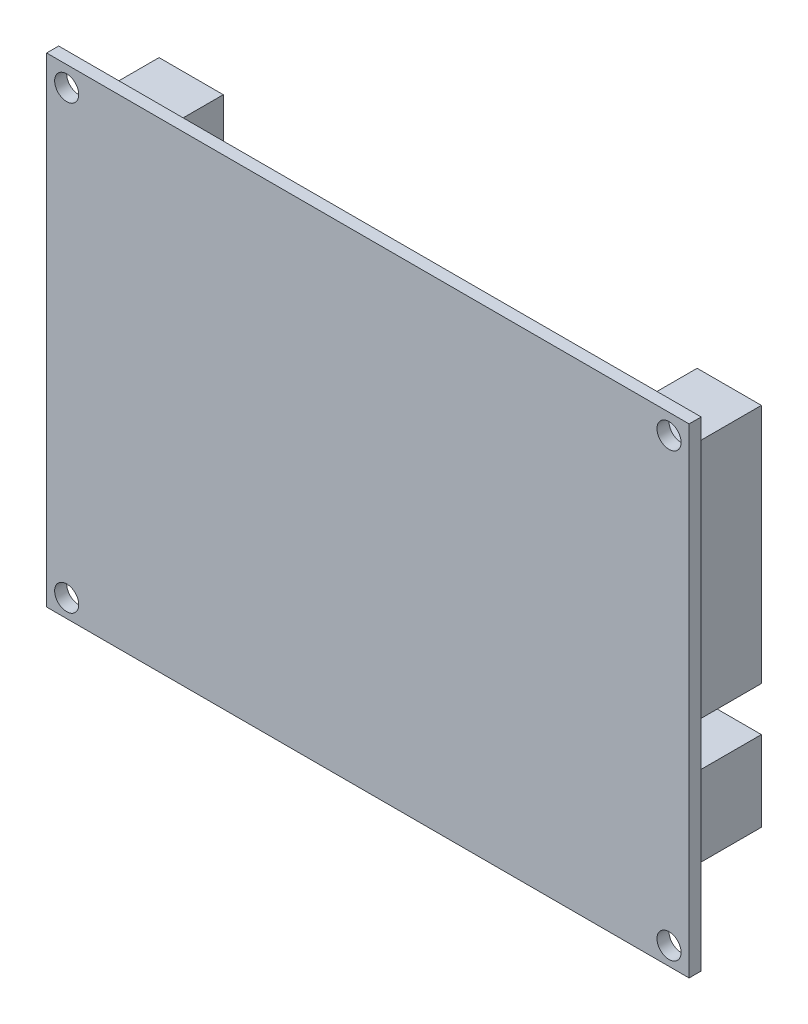
SolidWorks part; units mm, degrees
ref_plane "Front Plane" through (0, 0, 0) normal (0, 0, 1) x (1, 0, 0)
ref_plane "Top Plane" through (0, 0, 0) normal (0, 1, 0) x (1, 0, 0)
ref_plane "Right Plane" through (0, 0, 0) normal (1, 0, 0) x (0, 0, -1)
sketch "Sketch1" plane through (0, 0, 0) normal (0, 0, 1) x (1, 0, 0)
  line L0 (-35.4983, 34.528) -> (39.5017, 34.528)
  line L1 (-37.9983, 37.028) -> (42.0017, 37.028)
  line L2 (-37.9983, 37.028) -> (-37.9983, -22.972)
  line L3 (-37.9983, -22.972) -> (42.0017, -22.972)
  line L4 (42.0017, 37.028) -> (42.0017, -22.972)
  line L5 (39.5017, 34.528) -> (39.5017, -20.472)
  line L6 (-35.4983, -20.472) -> (39.5017, -20.472)
  line L7 (-35.4983, 34.528) -> (-35.4983, -20.472)
  line L8 (-37.9983, 32.028) -> (42.0017, 32.028)
  line L9 (39.5017, -3.472) -> (31.5017, -3.472)
  line L10 (39.5017, 32.028) -> (31.5017, 32.028)
  line L11 (39.5017, 32.028) -> (39.5017, 2.028)
  line L12 (39.5017, 2.028) -> (31.5017, 2.028)
  line L13 (31.5017, 32.028) -> (31.5017, 2.028)
  line L14 (-37.9983, -22.722) -> (42.0017, -22.722)
  line L15 (31.5017, -3.472) -> (39.5017, -3.472)
  line L16 (31.5017, -3.472) -> (31.5017, -13.472)
  line L17 (31.5017, -13.472) -> (39.5017, -13.472)
  line L18 (39.5017, -3.472) -> (39.5017, -13.472)
  line L19 (-35.4983, -14.472) -> (-15.4983, -14.472)
  line L20 (-35.4983, -22.722) -> (-15.4983, -22.722)
  line L21 (-35.4983, -22.722) -> (-35.4983, -14.722)
  line L22 (-35.4983, -14.722) -> (-15.4983, -14.722)
  line L23 (-15.4983, -22.722) -> (-15.4983, -14.722)
  line L24 (-37.9983, 19.028) -> (42.0017, 19.028)
  line L25 (-35.4983, -14.472) -> (-28.4983, -14.472)
  line L26 (-35.4983, -14.472) -> (-35.4983, -6.472)
  line L27 (-35.4983, -6.472) -> (-28.4983, -6.472)
  line L28 (-28.4983, -14.472) -> (-28.4983, -6.472)
  line L30 (-35.4983, 19.028) -> (14.5017, 19.028)
  line L31 (-35.4983, 19.028) -> (-35.4983, -5.972)
  line L32 (-35.4983, -5.972) -> (14.5017, -5.972)
  line L33 (14.5017, 19.028) -> (14.5017, -5.972)
  line L34 (-35.4983, 32.028) -> (-27.4983, 32.028)
  line L35 (-35.4983, 32.028) -> (-35.4983, 22.028)
  line L36 (-35.4983, 22.028) -> (-27.4983, 22.028)
  line L37 (-27.4983, 32.028) -> (-27.4983, 22.028)
  circle A0 centre (-35.4983, 34.528) radius 1.5
  circle A1 centre (39.5017, 34.528) radius 1.5
  circle A2 centre (-35.4983, -20.472) radius 1.5
  circle A3 centre (39.5017, -20.472) radius 1.5
  dimension "D4" = 5
  dimension "D1" = 60
  dimension "D2" = 80
  dimension "D5" = 8
  dimension "D6" = 30
  dimension "D8" = 10
  dimension "D10" = 8
  dimension "D11" = 20
  dimension "D13" = 7
  dimension "D14" = 8
  dimension "D16" = 25
  dimension "D17" = 50
  dimension "D18" = 10
  dimension "D19" = 8
  dimension "D3" = 2.5
  dimension "D7" = 5.5
  dimension "D9" = 0.25
  dimension "D12" = 0.25
  dimension "D15" = 18
extrude "Boss-Extrude1" add sketch "Sketch1" against normal blind 1.5 contours L8 L37 L36 L7 L24 L13 | A1 L5 L8 L4 L1 L2 L7 A0 L0 | A1 L0 A0 L7 L8 L5 | L2 L24 L7 L8 | L37 L8 L7 L36 | A2 L7 L24 L2 L14 L21 | L33 L24 L7 L32 | A3 L5 L17 L16 L9 L12 L13 L24 L33 L32 L7 L27 L28 L19 L22 L23 L6 | L13 L24 L5 L8 | L24 L13 L12 L11 | L5 L24 L4 L8 | A3 L6 L23 L14 L4 L24 L11 L5 | L16 L17 L5 L9 | A2 L6 L23 L22 L7 | A2 L21 L14 L23 L6 | L19 L28 L27 L7 region at (2.0017, 35.6777, 0) region at (2.0017, 33.2662, 0) region at (-31.4983, 27.028, 0) region at (-36.7483, 25.528, 0) region at (0.9852, 25.3763, 0) region at (40.7517, 25.528, 0) region at (35.5017, 25.528, 0) region at (-10.4983, 6.528, 0) region at (-36.7698, -1.1942, 0) region at (40.7517, 18.3174, 0) region at (35.5017, 10.528, 0) region at (12.1173, -6.3516, 0) region at (-31.9983, -10.472, 0) region at (-25.1156, -21.617, 0) region at (35.5017, -8.472, 0) region at (-25.3522, -17.5621, 0)
extrude "Boss-Extrude2" add sketch "Sketch1<8>" against normal blind 1.5 from offset 1.75 separate body contours L33 L24 L7 L32 region at (-10.4983, 6.528, 0) offset against normal yes
sketch "Sketch1<8>" plane through (0, 0, 0) normal (0, 0, 1) x (1, 0, 0) same geometry as "Sketch1"
extrude "Boss-Extrude3" add sketch "Sketch1<9>" against normal blind 10 from surface contours L37 L8 L7 L36 | L13 L24 L5 L8 | L24 L13 L12 L11 | L16 L17 L5 L9 | A2 L6 L23 L22 L7 | A2 L21 L14 L23 L6 region at (-31.4983, 27.028, 0) region at (35.5017, 25.528, 0) region at (35.5017, 10.528, 0) region at (-25.1156, -21.617, 0) region at (35.5017, -8.472, 0) region at (-25.3522, -17.5621, 0) starting at face at (-33.9983, -20.472, -1.5)
sketch "Sketch1<9>" plane through (0, 0, 0) normal (0, 0, 1) x (1, 0, 0) same geometry as "Sketch1"
extrude "Boss-Extrude4" add sketch "Sketch1<10>" against normal blind 8 from surface contours L19 L28 L27 L7 region at (-31.9983, -10.472, 0) starting at face at (35.5017, -8.472, -1.5)
sketch "Sketch1<10>" plane through (0, 0, 0) normal (0, 0, 1) x (1, 0, 0) same geometry as "Sketch1"
